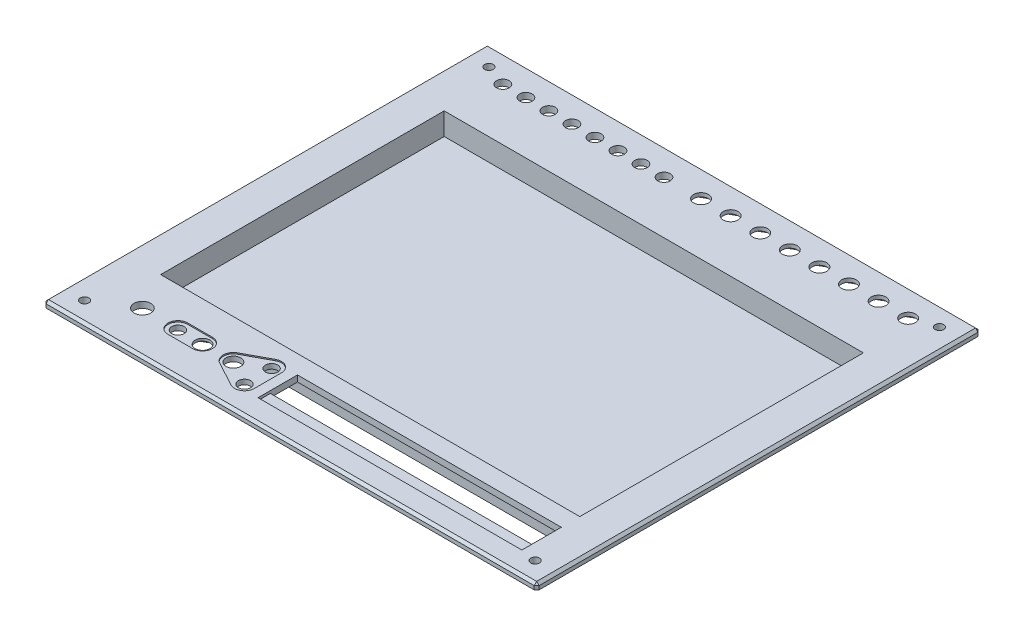
SolidWorks part; units mm, degrees
ref_plane "Alzado" through (0, 0, 0) normal (0, 0, 1) x (1, 0, 0)
ref_plane "Planta" through (0, 0, 0) normal (0, 1, 0) x (1, 0, 0)
ref_plane "Vista lateral" through (0, 0, 0) normal (1, 0, 0) x (0, 0, -1)
sketch "Croquis1" plane through (0, 0, 0) normal (1, 0, 0) x (0, 0, -1)
  line L0 (-90, 6.9261) -> (-90, 45)
  line L1 (-90, 45) -> (90, 45)
  line L2 (90, 45) -> (90, 6.9261)
  line L3 (-90, 6.9261) -> (-87.7, 5)
  line L4 (-87.7, 5) -> (-87.7, 0)
  line L5 (0, 0) -> (0, 88.9733) construction
  line L6 (87.7, 5) -> (87.7, 0)
  line L7 (90, 6.9261) -> (87.7, 5)
  line L8 (-85.2, 6.1672) -> (-85.2, 0)
  line L9 (-87.5, 8.0934) -> (-85.2, 6.1672)
  line L10 (-87.5, 8.0934) -> (-87.5, 42.5)
  line L11 (-87.5, 42.5) -> (87.5, 42.5)
  line L12 (87.5, 42.5) -> (87.5, 8.0934)
  line L13 (87.5, 8.0934) -> (85.2, 6.1672)
  line L14 (85.2, 6.1672) -> (85.2, 0)
  line L15 (85.2, 0) -> (87.7, 0)
  line L16 (-87.7, 0) -> (-85.2, 0)
  point P5 (0, 45)
  dimension "D3" = 5
  dimension "D4" = 45
  dimension "D1" = 180
  dimension "D2" = 3
  dimension "D5" = 2.3
  dimension "D6" = 2.5
extrude "Saliente-Extruir1" add sketch "Croquis1" along normal blind 200 contours L0 L1 L2 L7 L6 L15 L14 L13 L12 L11 L10 L9 L8 L16 L4 L3
sketch "Croquis2" plane through (0, 45, 0) normal (0, 1, 0) x (1, 0, 0)
  line L0 (200, -90) -> (0, -90) construction
  line L1 (189, 60) -> (11, 60)
  line L2 (189, 60) -> (189, -60)
  line L3 (189, -60) -> (11, -60)
  line L4 (11, 60) -> (11, -60)
  line L5 (189, 60) -> (11, -60) construction
  line L6 (189, -60) -> (11, 60) construction
  point P0 (100, 0)
  point P10 (100, -90)
  dimension "D1" = 120
  dimension "D2" = 178
extrude "Saliente-Extruir2" add sketch "Croquis2" against normal blind 11 contours L1 L4 L3 L2
sketch "Croquis3" plane through (0, 45, 0) normal (0, 1, 0) x (1, 0, 0)
  line L0 (200, -90) -> (0, -90) construction
  line L1 (15, 57.5) -> (185, 57.5)
  line L2 (15, 57.5) -> (15, -57.5)
  line L3 (15, -57.5) -> (185, -57.5)
  line L4 (185, 57.5) -> (185, -57.5)
  line L5 (15, 57.5) -> (185, -57.5) construction
  line L6 (15, -57.5) -> (185, 57.5) construction
  line L8 (0, -90) -> (0, 90) construction
  point P0 (100, 0)
  point P8 (100, -90)
  point P13 (0, 0)
  dimension "D1" = 170
  dimension "D2" = 115
extrude "Cortar-Extruir1" cut sketch "Croquis3" against normal blind 9
sketch "Croquis4" plane through (0, 0, 0) normal (0, -1, 0) x (-1, 0, 0)
  line L0 (-200, -90) -> (0, -90) construction
  line L1 (-200, 80) -> (-197.5, 80)
  line L2 (-200, 80) -> (-200, -90)
  line L3 (-200, -90) -> (-197.5, -90)
  line L4 (-197.5, 80) -> (-197.5, -90)
  line L5 (-200, 80) -> (-197.5, -90) construction
  line L6 (-200, -90) -> (-197.5, 80) construction
  line L7 (-200, -87.5) -> (-200, 87.5) construction
  line L8 (-200, 90) -> (0, 90) construction
  line L9 (-2.5, 90) -> (0, 90)
  line L10 (-2.5, 90) -> (-2.5, -90)
  line L11 (-2.5, -90) -> (0, -90)
  line L12 (0, 90) -> (0, -90)
  line L13 (-2.5, 90) -> (0, -90) construction
  line L14 (-2.5, -90) -> (0, 90) construction
  line L15 (0, -87.5) -> (0, 87.5) construction
  point P0 (-198.75, -5)
  point P9 (-1.25, 0)
  dimension "D1" = 2.5
  dimension "D2" = 2.5
extrude "Cortar-Extruir2" cut sketch "Croquis4" against normal up to surface (42.5 mm away) up to face at (100, 42.5, 0)
sketch "Croquis5" plane through (0, 45, 0) normal (0, 1, 0) x (1, 0, 0)
  line L0 (185, 57.5) -> (185, 90) construction
  line L1 (185, -57.5) -> (185, 57.5) construction
  line L2 (185, -57.5) -> (185, 57.5) construction
  line L3 (200, 90) -> (0, 90) construction
  line L4 (188.3221, 78.75) -> (90.1119, 78.75) construction
  line L6 (177.1619, 78.75) -> (179.5434, 74.625) construction
  line L7 (179.5434, 74.625) -> (184.3066, 74.625) construction
  line L8 (184.3066, 74.625) -> (186.6881, 78.75) construction
  line L9 (186.6881, 78.75) -> (184.3066, 82.875) construction
  line L10 (184.3066, 82.875) -> (179.5434, 82.875) construction
  line L11 (179.5434, 82.875) -> (177.1619, 78.75) construction
  circle A0 centre (181.925, 78.75) radius 3.075
  circle A1 centre (169.925, 78.75) radius 3.075
  circle A2 centre (157.925, 78.75) radius 3.075
  circle A3 centre (145.925, 78.75) radius 3.075
  circle A4 centre (133.925, 78.75) radius 3.075
  circle A5 centre (121.925, 78.75) radius 3.075
  circle A6 centre (109.925, 78.75) radius 3.075
  circle A7 centre (97.925, 78.75) radius 3.075
  circle A8 centre (181.925, 78.75) radius 4.125 construction
  dimension "D1" = 6.15
  dimension "D3" = 11.25
  dimension "D4" = 12
  dimension "D5" = 8.25
  dimension "D2" = 8
extrude "Cortar-Extruir3" cut sketch "Croquis5" against normal blind 10
sketch "Croquis6" plane through (0, 34, 0) normal (0, -1, 0) x (1, 0, 0)
  line L0 (185.925, -81.0594) -> (185.925, -76.4406)
  line L1 (177.925, -76.4406) -> (177.925, -81.0594)
  line L2 (177.925, -81.0594) -> (181.925, -83.3688)
  line L3 (181.925, -83.3688) -> (185.925, -81.0594)
  line L4 (185.925, -76.4406) -> (181.925, -74.1312)
  line L5 (181.925, -74.1312) -> (177.925, -76.4406)
  line L6 (169.925, -74.1312) -> (165.925, -76.4406)
  line L7 (165.925, -81.0594) -> (169.925, -83.3688)
  line L8 (169.925, -83.3688) -> (173.925, -81.0594)
  line L9 (173.925, -81.0594) -> (173.925, -76.4406)
  line L10 (165.925, -76.4406) -> (165.925, -81.0594)
  line L11 (173.925, -76.4406) -> (169.925, -74.1312)
  line L12 (157.925, -74.1312) -> (153.925, -76.4406)
  line L13 (153.925, -81.0594) -> (157.925, -83.3688)
  line L14 (157.925, -83.3688) -> (161.925, -81.0594)
  line L15 (161.925, -81.0594) -> (161.925, -76.4406)
  line L16 (153.925, -76.4406) -> (153.925, -81.0594)
  line L17 (161.925, -76.4406) -> (157.925, -74.1312)
  line L18 (145.925, -74.1312) -> (141.925, -76.4406)
  line L19 (141.925, -81.0594) -> (145.925, -83.3688)
  line L20 (145.925, -83.3688) -> (149.925, -81.0594)
  line L21 (149.925, -81.0594) -> (149.925, -76.4406)
  line L22 (141.925, -76.4406) -> (141.925, -81.0594)
  line L23 (149.925, -76.4406) -> (145.925, -74.1312)
  line L24 (133.925, -74.1312) -> (129.925, -76.4406)
  line L25 (129.925, -81.0594) -> (133.925, -83.3688)
  line L26 (133.925, -83.3688) -> (137.925, -81.0594)
  line L27 (137.925, -81.0594) -> (137.925, -76.4406)
  line L28 (129.925, -76.4406) -> (129.925, -81.0594)
  line L29 (137.925, -76.4406) -> (133.925, -74.1312)
  line L30 (121.925, -74.1312) -> (117.925, -76.4406)
  line L31 (117.925, -81.0594) -> (121.925, -83.3688)
  line L32 (121.925, -83.3688) -> (125.925, -81.0594)
  line L33 (125.925, -81.0594) -> (125.925, -76.4406)
  line L34 (117.925, -76.4406) -> (117.925, -81.0594)
  line L35 (125.925, -76.4406) -> (121.925, -74.1312)
  line L36 (109.925, -74.1312) -> (105.925, -76.4406)
  line L37 (105.925, -81.0594) -> (109.925, -83.3688)
  line L38 (109.925, -83.3688) -> (113.925, -81.0594)
  line L39 (113.925, -81.0594) -> (113.925, -76.4406)
  line L40 (105.925, -76.4406) -> (105.925, -81.0594)
  line L41 (113.925, -76.4406) -> (109.925, -74.1312)
  line L42 (97.925, -74.1312) -> (93.925, -76.4406)
  line L43 (93.925, -81.0594) -> (97.925, -83.3688)
  line L44 (97.925, -83.3688) -> (101.925, -81.0594)
  line L45 (101.925, -81.0594) -> (101.925, -76.4406)
  line L46 (93.925, -76.4406) -> (93.925, -81.0594)
  line L47 (101.925, -76.4406) -> (97.925, -74.1312)
  circle A0 centre (181.925, -78.75) radius 4 construction
  circle A1 centre (169.925, -78.75) radius 4 construction
  circle A2 centre (157.925, -78.75) radius 4 construction
  circle A3 centre (145.925, -78.75) radius 4 construction
  circle A4 centre (133.925, -78.75) radius 4 construction
  circle A5 centre (121.925, -78.75) radius 4 construction
  circle A6 centre (109.925, -78.75) radius 4 construction
  circle A7 centre (97.925, -78.75) radius 4 construction
  dimension "D1" = 8
  dimension "D2" = 8
extrude "Cortar-Extruir4" cut sketch "Croquis6" against normal blind 11.2
sketch "Croquis7" plane through (0, 45, 0) normal (0, 1, 0) x (1, 0, 0)
  line L0 (0, 78.75) -> (85.4351, 78.75) construction
  line L2 (0, -90) -> (0, 90) construction
  line L3 (200, 90) -> (0, 90) construction
  line L4 (15, 57.5) -> (15, 90) construction
  circle A1 centre (82.8851, 78.75) radius 2.55
  circle A2 centre (73.5515, 78.75) radius 2.55
  circle A3 centre (64.2179, 78.75) radius 2.55
  circle A4 centre (54.8843, 78.75) radius 2.55
  circle A5 centre (45.5507, 78.75) radius 2.55
  circle A6 centre (36.2172, 78.75) radius 2.55
  circle A7 centre (26.8836, 78.75) radius 2.55
  circle A8 centre (17.55, 78.75) radius 2.55
  dimension "D1" = 5.1
  dimension "D4" = 65.3351
  dimension "D3" = 11.25
  dimension "D2" = 8
extrude "Cortar-Extruir5" cut sketch "Croquis7" against normal blind 10
sketch "Croquis9" plane through (0, 45, 0) normal (0, 1, 0) x (1, 0, 0)
  line L1 (185, -81) -> (78, -81)
  line L2 (185, -81) -> (185, -65)
  line L3 (185, -65) -> (78, -65)
  line L4 (78, -81) -> (78, -65)
  line L5 (185, -81) -> (78, -65) construction
  line L6 (185, -65) -> (78, -81) construction
  line L7 (185, -57.5) -> (185, 57.5) construction
  line L8 (200, -90) -> (0, -90) construction
  point P0 (131.5, -73)
  dimension "D1" = 107
  dimension "D2" = 16
  dimension "D3" = 17
extrude "Cortar-Extruir7" cut sketch "Croquis9" against normal blind 4
sketch "Croquis8" plane through (0, 45, 0) normal (0, 1, 0) x (1, 0, 0)
  line L0 (47.5, -73) -> (47.5, -77.6188) construction
  line L1 (63, -73) -> (15, -73) construction
  line L2 (47.5, -77.6188) -> (51.5, -75.3094) construction
  line L3 (15, 57.5) -> (15, -57.5) construction
  line L4 (200, -90) -> (0, -90) construction
  line L5 (0, -90) -> (0, 90) construction
  line L6 (51.5, -75.3094) -> (51.5, -70.6906) construction
  line L7 (51.5, -70.6906) -> (47.5, -68.3812) construction
  line L8 (47.5, -68.3812) -> (43.5, -70.6906) construction
  line L9 (43.5, -70.6906) -> (43.5, -75.3094) construction
  line L10 (43.5, -75.3094) -> (47.5, -77.6188) construction
  line L11 (63, -73) -> (70, -73) construction
  line L12 (70, -73) -> (70, -78.5) construction
  line L13 (70, -78.5) -> (60, -73) construction
  line L14 (60, -73) -> (70, -67.5) construction
  line L15 (70, -67.5) -> (70, -73) construction
  line L18 (78, -81) -> (63, -81) construction
  line L19 (78, -65) -> (62.9966, -65) construction
  circle A0 centre (60, -73) radius 3
  circle A1 centre (37.5, -73) radius 2.5
  circle A2 centre (23.1, -73) radius 3.4
  circle A3 centre (23.1, -73) radius 8.1 construction
  circle A4 centre (70, -73) radius 2.5 construction
  circle A5 centre (47.5, -73) radius 3
  circle A6 centre (47.5, -73) radius 4 construction
  circle A7 centre (70, -78.5) radius 2.5
  circle A8 centre (70, -67.5) radius 2.5
  dimension "D1" = 6
  dimension "D2" = 17
  dimension "D3" = 5
  dimension "D5" = 6.8
  dimension "D7" = 16.2
  dimension "D4" = 5
  dimension "D6" = 6
  dimension "D10" = 70
  dimension "D11" = 60
  dimension "D14" = 5
  dimension "D15" = 5
  dimension "D8" = 37.5
  dimension "D9" = 47.5
  dimension "D12" = 23.1
  dimension "D13" = 8
extrude "Cortar-Extruir6" cut sketch "Croquis8" against normal blind 4
sketch "Croquis11" plane through (0, 42.5, 0) normal (0, -1, 0) x (1, 0, 0)
  line L0 (47.5, 73) -> (47.5, 77.6188) construction
  line L1 (47.5, 4691.3588) -> (-3952.116, 2382.1794)
  line L2 (-3952.116, 2382.1794) -> (-3952.116, -2236.1794)
  line L3 (-3952.116, -2236.1794) -> (47.5, -4545.3588)
  line L4 (47.5, -4545.3588) -> (4047.116, -2236.1794)
  line L5 (4047.116, -2236.1794) -> (4047.116, 2382.1794)
  line L6 (4047.116, 2382.1794) -> (47.5, 4691.3588)
  line L7 (47.5, 68.3812) -> (51.5, 70.6906)
  line L8 (51.5, 70.6906) -> (51.5, 75.3094)
  line L9 (51.5, 75.3094) -> (47.5, 77.6188)
  line L10 (47.5, 77.6188) -> (43.5, 75.3094)
  line L11 (43.5, 75.3094) -> (43.5, 70.6906)
  line L12 (43.5, 70.6906) -> (47.5, 68.3812)
  circle A0 centre (47.5, 73) radius 3999.616 construction
  circle A1 centre (47.5, 73) radius 4 construction
  dimension "D1" = 8
extrude "Cortar-Extruir10" cut sketch "Croquis11" against normal blind 1 flip side to cut
sketch "Croquis12" plane through (0, 45, 0) normal (0, 1, 0) x (1, 0, 0)
  line L0 (68.1021, -82.0211) -> (58.0562, -76.6061)
  line L1 (68.1021, -63.9789) -> (58.0562, -69.3939)
  line L2 (74, -78.5) -> (74, -67.5)
  line L3 (47.5, -73) -> (37.5, -73) construction
  line L4 (47.5, -77) -> (37.5, -77)
  line L5 (47.5, -69) -> (37.5, -69)
  circle A0 centre (70, -67.5) radius 3 construction
  arc A2 (74, -67.5) -> (68.1021, -63.9789) centre (70, -67.5) ccw
  arc A3 (68.1021, -82.0211) -> (74, -78.5) centre (70, -78.5) ccw
  arc A10 (47.5, -77) -> (47.5, -69) centre (47.5, -73) ccw
  arc A11 (37.5, -69) -> (37.5, -77) centre (37.5, -73) ccw
  circle A12 centre (47.5, -73) radius 3 construction
  circle A13 centre (37.5, -73) radius 3 construction
  arc A14 (58.0562, -69.3939) -> (58.0562, -76.6061) centre (60, -73) ccw
  circle A15 centre (60, -73) radius 3 construction
  circle A16 centre (70, -78.5) radius 3 construction
  point P16 (42.5, -73)
  point P21 (33.5, -73)
  point P24 (51.5, -73)
  dimension "D3" = 6
  dimension "D1" = 1.0966
  dimension "D2" = 6
  dimension "D5" = 6
  dimension "D7" = 1
  dimension "D8" = 1
  dimension "D4" = 1
  dimension "D6" = 1
extrude "Cortar-Extruir11" cut sketch "Croquis12" against normal blind 0.5
sketch "Croquis13" plane through (0, 0, 0) normal (-1, 0, 0) x (0, 0, 1)
  line L1 (-90, 42.5) -> (-68.4479, 42.5)
  line L2 (-90, 42.5) -> (-90, -26.0307)
  line L3 (-90, -26.0307) -> (-68.4479, -26.0307)
  line L4 (-68.4479, 42.5) -> (-68.4479, -26.0307)
  line L5 (90, 42.5) -> (71.0662, 42.5)
  line L6 (90, 42.5) -> (90, -36.6906)
  line L7 (90, -36.6906) -> (71.0662, -36.6906)
  line L8 (71.0662, 42.5) -> (71.0662, -36.6906)
extrude "Cortar-Extruir12" cut sketch "Croquis13" against normal through all
sketch "Croquis18" plane through (0, 42.5, 0) normal (0, -1, 0) x (1, 0, 0)
  line L0 (0, -90) -> (200, -90) construction
  line L1 (200, 90) -> (200, -90) construction
  line L2 (0, 0) -> (200, 0) construction
  line L3 (100, 0) -> (100, -50000) construction
  circle A0 centre (191.36, -82) radius 1.75
  circle A1 centre (8.64, -82) radius 1.75
  circle A2 centre (8.64, 82) radius 1.75
  circle A3 centre (191.36, 82) radius 1.75
  dimension "D1" = 8
  dimension "D2" = 8.64
extrude "Cortar-Extruir13" cut sketch "Croquis18" against normal through all
sketch "Croquis20" plane through (0, 0, -60) normal (0, 0, -1) x (-1, 0, 0)
  line L4 (-11, 42.5) -> (-189, 42.5)
  line L5 (-189, 42.5) -> (-189, 34)
  line L6 (-189, 34) -> (-11, 34)
  line L7 (-11, 34) -> (-11, 42.5)
  line L8 (-11, 42.5) -> (-189, 42.5)
  line L9 (-189, 42.5) -> (-189, 34)
  line L10 (-189, 34) -> (-11, 34)
  line L11 (-11, 34) -> (-11, 42.5)
  dimension "D1" = 0
sketch "Croquis21" plane through (0, 0, -60) normal (0, 0, -1) x (-1, 0, 0)
  line L0 (-189, 42.5) -> (-11, 42.5) construction
  line L1 (-11, 34) -> (-106.6, 34)
  line L2 (-11, 34) -> (-11, 42.5)
  line L3 (-11, 42.5) -> (-106.6, 42.5)
  line L4 (-106.6, 34) -> (-106.6, 42.5)
extrude "Saliente-Extruir3" add sketch "Croquis21" along normal blind 5
sketch "Croquis22" plane through (11, 0, 0) normal (-1, 0, 0) x (0, 0, 1)
  line L0 (90, 42.5) -> (-90, 42.5) construction
  line L1 (-65, 42.5) -> (14.9356, 42.5)
  line L2 (-65, 42.5) -> (-65, 34)
  line L3 (-65, 34) -> (14.9356, 34)
  line L4 (14.9356, 42.5) -> (14.9356, 34)
  line L5 (-65, 34) -> (-65, 42.5) construction
  line L6 (-65, 34) -> (60, 34) construction
extrude "Saliente-Extruir4" add sketch "Croquis22" along normal blind 8
sketch "Croquis24" plane through (78, 0, 0) normal (1, 0, 0) x (0, 0, -1)
  line L0 (-81, 45) -> (-81, 44) construction
  line L1 (-81, 42.5) -> (-81, 45) construction
  line L2 (-81, 44) -> (-76, 44) construction
  line L3 (-76, 44) -> (-76, 41) construction
  line L4 (-76, 41) -> (-83, 41) construction
  line L5 (-83, 41) -> (-83, 42.5) construction
  line L6 (-83, 42.5) -> (-84.5, 42.5) construction
  line L7 (-84.5, 42.5) -> (-83, 41)
  line L8 (-83, 41) -> (-76, 41)
  line L9 (-76, 41) -> (-76, 44)
  line L10 (-76, 44) -> (-80, 44)
  line L11 (-80, 44) -> (-81, 45)
  line L12 (-81, 45) -> (-81, 42.5)
  line L13 (-81, 42.5) -> (-84.5, 42.5)
extrude "Saliente-Extruir5" add sketch "Croquis24" along normal up to surface (107 mm away) up to face at (185, 43.75, 73)
sketch "Croquis25" plane through (0, 45, 0) normal (0, 1, 0) x (1, 0, 0)
  line L0 (177.925, 81.0594) -> (177.925, 76.4406) construction
  line L1 (181.925, 74.1312) -> (185.925, 76.4406)
  line L2 (185.925, 76.4406) -> (185.925, 81.0594)
  line L3 (185.925, 81.0594) -> (181.925, 83.3688)
  line L4 (181.925, 83.3688) -> (177.925, 81.0594)
  line L5 (177.925, 81.0594) -> (177.925, 76.4406)
  line L6 (177.925, 76.4406) -> (181.925, 74.1312)
  line L7 (185.925, 76.4406) -> (185.925, 81.0594) construction
  line L8 (181.925, 74.1312) -> (185.925, 76.4406) construction
  circle A0 centre (181.925, 78.75) radius 4 construction
  circle A1 centre (181.925, 78.75) radius 3
  dimension "D1" = 6
extrude "Saliente-Extruir6" add sketch "Croquis25" against normal blind 1.5
pattern_linear "MatrizL1" count 8 spacing 12 along (-1, 0, 0) of "Saliente-Extruir6"
chamfer "Chaflán1" distance 1 angle 45 8 edges at (0, 43.75, 90) (0, 45, 0) (0, 43.75, -90) (100, 45, -90) (200, 43.75, -90) (100, 45, 90) (200, 43.75, 90) (200, 45, 0)
